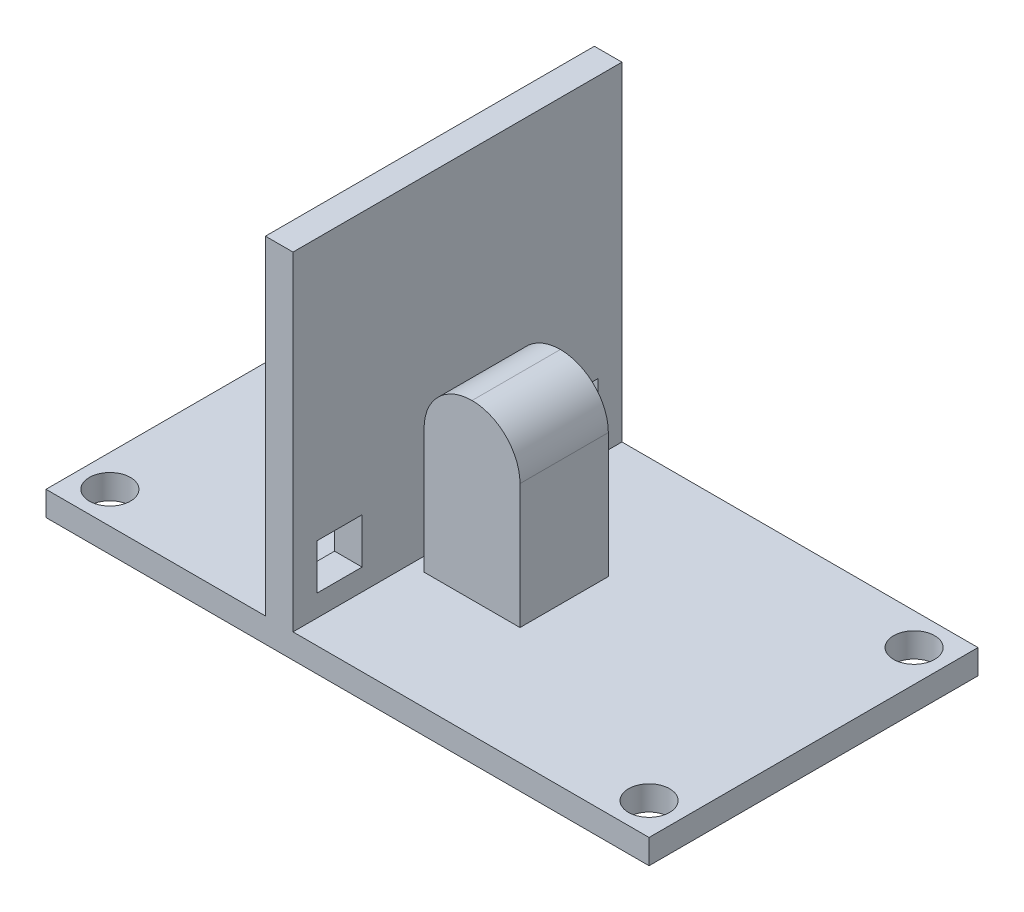
SolidWorks part; units mm, degrees
ref_plane "Front Plane" through (0, 0, 0) normal (0, 0, 1) x (1, 0, 0)
ref_plane "Top Plane" through (0, 0, 0) normal (0, 1, 0) x (1, 0, 0)
ref_plane "Right Plane" through (0, 0, 0) normal (1, 0, 0) x (0, 0, -1)
sketch "Sketch1" plane through (0, 0, 0) normal (0, 1, 0) x (1, 0, 0)
  line L1 (-57.735, 7.9136) -> (12.115, 7.9136)
  line L2 (-57.735, 7.9136) -> (-57.735, -30.1864)
  line L3 (-57.735, -30.1864) -> (12.115, -30.1864)
  line L4 (12.115, 7.9136) -> (12.115, -30.1864)
  dimension "D1" = 38.1
  dimension "D2" = 69.85
extrude "Boss-Extrude1" add sketch "Sketch1" along normal blind 2.84
sketch "Sketch2" plane through (0, 2.84, 0) normal (0, 1, 0) x (1, 0, 0)
  line L0 (12.115, 7.9136) -> (-57.735, 7.9136) construction
  line L1 (-27.525, -6.3764) -> (-16.4125, -6.3764)
  line L2 (-27.525, -6.3764) -> (-27.525, -16.6064)
  line L3 (-27.525, -16.6064) -> (-16.4125, -16.6064)
  line L4 (-16.4125, -6.3764) -> (-16.4125, -16.6064)
  line L5 (12.115, -30.1864) -> (12.115, 7.9136) construction
  dimension "D1" = 14.29
  dimension "D2" = 39.64
  dimension "D3" = 11.1125
  dimension "D4" = 10.23
extrude "Boss-Extrude5" add sketch "Sketch2" along normal blind 20
sketch "Sketch4" plane through (0, 2.84, 0) normal (0, 1, 0) x (1, 0, 0)
  line L0 (-27.525, -6.3764) -> (-27.525, -16.6064) construction
  line L1 (-29.125, 7.9136) -> (-32.3172, 7.9136)
  line L2 (-29.125, 7.9136) -> (-29.125, -30.1864)
  line L3 (-29.125, -30.1864) -> (-32.3172, -30.1864)
  line L4 (-32.3172, 7.9136) -> (-32.3172, -30.1864)
  line L5 (12.115, 7.9136) -> (-57.735, 7.9136) construction
  line L6 (-57.735, -30.1864) -> (12.115, -30.1864) construction
  dimension "D1" = 1.6
  dimension "D2" = 0
  dimension "D3" = 0
extrude "Boss-Extrude7" add sketch "Sketch4" along normal blind 38.1 contours L2 L3 L4 L1
fillet "Fillet1" radius 5.5563 1 edges at (-16.4125, 22.84, 11.4914)
fillet "Fillet2" radius 5.5563 1 edges at (-27.525, 22.84, 11.4914)
sketch "Sketch5" plane through (0, 2.84, 0) normal (0, 1, 0) x (1, 0, 0)
  line L0 (-32.3172, 7.9136) -> (-57.735, 7.9136) construction
  line L1 (-36.8172, -3.1364) -> (-44.8172, -3.1364)
  line L2 (-36.8172, -3.1364) -> (-36.8172, -17.6364)
  line L3 (-36.8172, -17.6364) -> (-44.8172, -17.6364)
  line L4 (-44.8172, -3.1364) -> (-44.8172, -17.6364)
  line L5 (-32.3172, 7.9136) -> (-32.3172, -30.1864) construction
  dimension "D1" = 8
  dimension "D2" = 14.5
  dimension "D3" = 11.05
  dimension "D4" = 4.5
extrude "Cut-Extrude1" cut sketch "Sketch5" against normal blind 38.1
sketch "Sketch6" plane through (-29.125, 0, 0) normal (1, 0, 0) x (0, 0, -1)
  line L0 (7.9136, 40.94) -> (7.9136, 2.84) construction
  line L1 (5.1636, 5.34) -> (-0.0864, 5.34)
  line L2 (5.1636, 5.34) -> (5.1636, 10.59)
  line L3 (5.1636, 10.59) -> (-0.0864, 10.59)
  line L4 (-0.0864, 5.34) -> (-0.0864, 10.59)
  line L5 (7.9136, 2.84) -> (-30.1864, 2.84) construction
  dimension "D1" = 5.25
  dimension "D2" = 5.25
  dimension "D3" = 2.75
  dimension "D4" = 2.5
extrude "Cut-Extrude2" cut sketch "Sketch6" against normal blind 10
sketch "Sketch7" plane through (-29.125, 0, 0) normal (1, 0, 0) x (0, 0, -1)
  line L0 (-30.1864, 40.94) -> (-30.1864, 2.84) construction
  line L1 (-22.1834, 5.34) -> (-27.4364, 5.34)
  line L2 (-22.1834, 5.34) -> (-22.1834, 10.59)
  line L3 (-22.1834, 10.59) -> (-27.4364, 10.59)
  line L4 (-27.4364, 5.34) -> (-27.4364, 10.59)
  line L5 (7.9136, 2.84) -> (-30.1864, 2.84) construction
  dimension "D1" = 5.253
  dimension "D2" = 5.25
  dimension "D3" = 2.75
  dimension "D4" = 2.5
extrude "Cut-Extrude3" cut sketch "Sketch7" against normal blind 10
sketch "Sketch8" plane through (0, 2.84, 0) normal (0, 1, 0) x (1, 0, 0)
  line L0 (12.115, 7.9136) -> (-29.125, 7.9136) construction
  line L1 (12.115, -30.1864) -> (12.115, 7.9136) construction
  circle A0 centre (8.415, 4.2136) radius 2.3813
  dimension "D1" = 3.7
  dimension "D2" = 3.7
extrude "Cut-Extrude4" cut sketch "Sketch8" against normal blind 10
sketch "Sketch9" plane through (0, 2.84, 0) normal (0, 1, 0) x (1, 0, 0)
  line L0 (12.115, -30.1864) -> (12.115, 7.9136) construction
  line L1 (-29.125, -30.1864) -> (12.115, -30.1864) construction
  circle A0 centre (8.415, -26.4864) radius 2.3813
  dimension "D1" = 3.7
  dimension "D2" = 3.7
extrude "Cut-Extrude5" cut sketch "Sketch9" against normal blind 10
sketch "Sketch10" plane through (0, 2.84, 0) normal (0, 1, 0) x (1, 0, 0)
  line L0 (-44.8172, -17.6364) -> (-36.8172, -17.6364) construction
  line L1 (-32.3172, -3.1364) -> (-36.8172, -3.1364)
  line L2 (-32.3172, -3.1364) -> (-32.3172, -17.6364)
  line L3 (-32.3172, -17.6364) -> (-36.8172, -17.6364)
  line L4 (-36.8172, -3.1364) -> (-36.8172, -17.6364)
  line L5 (-36.8172, -17.6364) -> (-36.8172, -3.1364) construction
  line L6 (-36.8172, -3.1364) -> (-44.8172, -3.1364) construction
  line L7 (-32.3172, 7.9136) -> (-32.3172, -30.1864) construction
  dimension "D1" = 0
  dimension "D2" = 0
extrude "Cut-Extrude6" cut sketch "Sketch10" against normal blind 10
sketch "Sketch12" plane through (0, 2.84, 0) normal (0, 1, 0) x (1, 0, 0)
  line L0 (-57.735, 7.9136) -> (-57.735, -30.1864) construction
  line L1 (-57.735, -30.1864) -> (-32.3172, -30.1864) construction
  circle A0 centre (-54.035, -26.4864) radius 2.3812
  dimension "D1" = 3.7
  dimension "D2" = 3.7
extrude "Cut-Extrude7" cut sketch "Sketch12" against normal blind 10
sketch "Sketch13" plane through (0, 2.84, 0) normal (0, 1, 0) x (1, 0, 0)
  line L0 (-57.735, 7.9136) -> (-57.735, -30.1864) construction
  line L1 (-32.3172, 7.9136) -> (-57.735, 7.9136) construction
  circle A0 centre (-54.035, 4.2136) radius 2.3812
  dimension "D1" = 3.7
  dimension "D2" = 3.7
extrude "Cut-Extrude8" cut sketch "Sketch13" against normal blind 10
